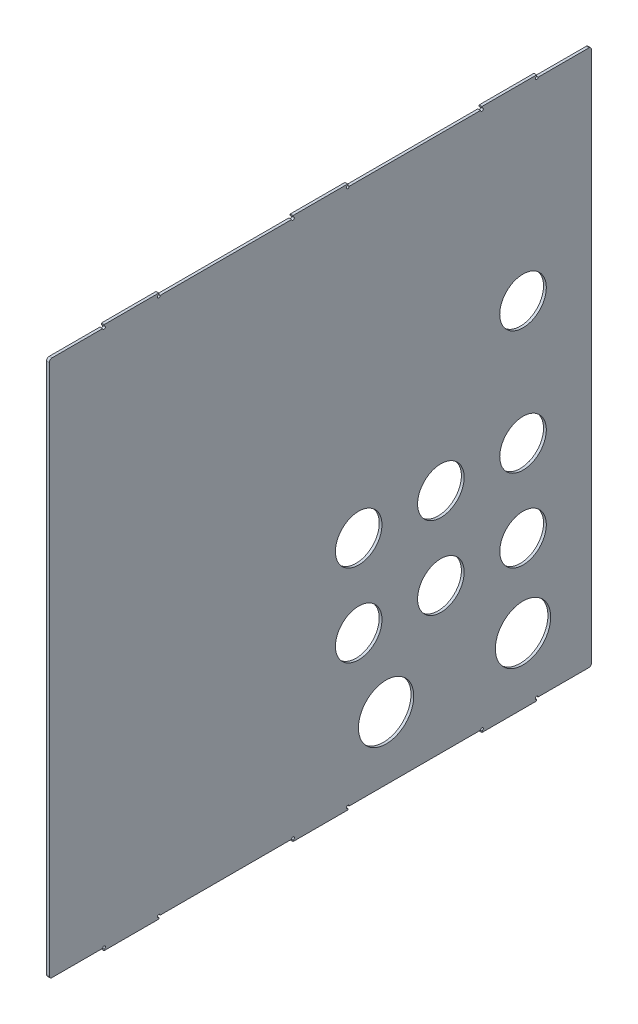
SolidWorks part; units mm, degrees
material "ASTM A36 Acier"
ref_plane "Front" through (0, 0, 0) normal (0, 0, 1) x (1, 0, 0)
ref_plane "Top" through (0, 0, 0) normal (0, 1, 0) x (1, 0, 0)
ref_plane "Right" through (0, 0, 0) normal (1, 0, 0) x (0, 0, -1)
sketch "Esquisse1" plane through (0, 0, 0) normal (1, 0, 0) x (0, 0, -1)
  line L0 (0, 99) -> (0, 0) construction
  line L1 (-99, -98) -> (-79, -98)
  line L2 (-99, -98) -> (-99, 98)
  line L3 (-99, 98) -> (-79, 98)
  line L4 (99, -98) -> (99, 98)
  line L5 (-99, -98) -> (99, 98) construction
  line L6 (-99, 98) -> (99, -98) construction
  line L8 (-10, 98) -> (-10, 99)
  line L9 (-10, 99) -> (10, 99)
  line L10 (10, 98) -> (10, 99)
  line L12 (59, 98) -> (59, 99)
  line L13 (59, 99) -> (79, 99)
  line L14 (79, 98) -> (79, 99)
  line L16 (-79, 98) -> (-79, 99)
  line L17 (-79, 99) -> (-59, 99)
  line L18 (-59, 98) -> (-59, 99)
  line L19 (-59, 98) -> (-10, 98)
  line L20 (10, 98) -> (59, 98)
  line L21 (79, 98) -> (99, 98)
  line L22 (-4.7942, 0) -> (-50004.7942, 0) construction
  line L23 (79, -98) -> (79, -99)
  line L24 (59, -99) -> (79, -99)
  line L25 (59, -98) -> (59, -99)
  line L26 (10, -98) -> (10, -99)
  line L27 (-10, -99) -> (10, -99)
  line L28 (-10, -98) -> (-10, -99)
  line L29 (-59, -98) -> (-59, -99)
  line L30 (-79, -98) -> (-79, -99)
  line L31 (-79, -99) -> (-59, -99)
  line L32 (-59, -98) -> (-10, -98)
  line L33 (10, -98) -> (59, -98)
  line L34 (79, -98) -> (99, -98)
  point P0 (0, 0)
  dimension "D1" = 196
  dimension "D2" = 198
  dimension "D3" = 1
  dimension "D4" = 20
  dimension "D5" = 20
  dimension "D6" = 20
base flange "Tôle de base pliée1" sketch "Esquisse1" thickness 1 reverse thickness direction no parameters "D1"=0.7366
sketch "Esquisse2" plane through (-1, 0, 0) normal (-1, 0, 0) x (0, 0, 1)
  line L12 (-99, 98) -> (-151.518, -98)
  line L13 (79, 98) -> (99, 98) construction
  line L14 (-99, -98) -> (-99, 98) construction
  line L15 (-151.518, -98) -> (-99, -98)
  line L16 (-99, -98) -> (-99, 98)
  line L17 (99, -98) -> (79, -98) construction
  dimension "D1" = 15
base flange "Patte1" [suppressed] sketch "Esquisse2" thickness 1 reverse thickness direction no parameters "D1"=0.7366
sketch "Esquisse4" plane through (-1, 0, 0) normal (-1, 0, 0) x (0, 0, 1)
  line L0 (72.0915, -45) -> (13.3317, -45) construction
  line L1 (67.0754, -15) -> (-49932.9246, -15) construction
  line L2 (-74, -75) -> (-74, -45) construction
  line L3 (-14, -15) -> (-14, -45) construction
  line L4 (99, 30) -> (-93.4567, 30) construction
  line L5 (-14, -45) -> (-14, 30) construction
  line L6 (-99, -98) -> (-99, 98) construction
  line L8 (-74, 30) -> (-74, -45) construction
  line L9 (-74, -75) -> (-24, -75) construction
  line L10 (-74, -45) -> (-44, -45) construction
  circle A0 centre (-14, -15) radius 8.5
  circle A1 centre (-14, -45) radius 8.5
  circle A2 centre (-44, -15) radius 8.5
  circle A3 centre (-44, -45) radius 8.5
  circle A4 centre (-74, -45) radius 8.5
  circle A8 centre (-74, 30) radius 8.5
  circle A9 centre (-74, -75) radius 10.1
  circle A11 centre (-74, -15) radius 8.5
  circle A12 centre (-24, -75) radius 10.1
  dimension "D3" = 17
  dimension "D4" = 30
  dimension "D7" = 30
  dimension "D10" = 17
  dimension "D11" = 15
  dimension "D13" = 30
  dimension "D14" = 20.2
  dimension "D2" = 45
  dimension "D5" = 0
  dimension "D6" = 0
  dimension "D8" = 30
  dimension "D9" = 50
  dimension "D12" = 25
  dimension "D15" = 75
extrude "Enlèv. mat.-Extru.1" cut sketch "Esquisse4" against normal through all normal cut yes
ref_plane "Plan1" through (-1, 0, 0) normal (-1, 0, 0) x (0, 0, 1)
sketch "Esquisse11" plane through (-1, 0, 0) normal (-1, 0, 0) x (0, 0, 1)
  line L0 (-109.0261, 5) -> (49890.9739, 5) construction
  line L1 (-114.3569, -5) -> (49885.6431, -5) construction
  line L2 (-74, 30) -> (-74, -5) construction
  line L3 (-89.6603, 42) -> (9.9385, 42) construction
  line L4 (-74, -15) -> (-74, -2) construction
  line L5 (-128.3704, 10) -> (49871.6296, 10) construction
  line L6 (-74.568, -2) -> (-11.5081, -2) construction
  line L7 (-44, -15) -> (-44, -2) construction
  line L8 (-14, -15) -> (-14, -2) construction
  line L9 (-167.5798, -33) -> (49832.4202, -33) construction
  line L10 (-74, -45) -> (-74, -33) construction
  line L11 (-44, -45) -> (-44, -33) construction
  line L12 (-14, -45) -> (-14, -33) construction
  line L13 (-99, -98) -> (-99, 98) construction
  circle A0 centre (-44, -15) radius 8.5 construction
  circle A1 centre (-74, -15) radius 8.5 construction
  circle A2 centre (-14, -45) radius 8.5 construction
  text T0 "THERMOCOUPLES" font "Varela Round" height in points 22
  text T4 "HEATERS" font "Varela Round" height in points 22
  text T5 "2" font "Varela Round" height in points 22
  text T6 "3" font "Varela Round" height in points 22
  text T7 "4" font "Varela Round" height in points 22
  text T8 "5" font "Varela Round" height in points 22
  text T9 "6" font "Varela Round" height in points 22
  text T10 "1" font "Varela Round" height in points 22
  dimension "D1" = 5
  dimension "D2" = 10
  dimension "D3" = 12
  dimension "D4" = 31
  dimension "D5" = 2.5
  dimension "D6" = 25
  dimension "D7" = 12
  dimension "D8" = 2.5
  dimension "D9" = 2.5
  dimension "D10" = 12
  dimension "D11" = 2.5
  dimension "D12" = 2.5
  dimension "D13" = 2.5
extrude "Enlèv. mat.-Extru.2" cut sketch "Esquisse11" against normal blind 0.5 normal cut yes
sketch "Esquisse12" plane through (0, 0, 0) normal (1, 0, 0) x (0, 0, -1)
  line L0 (0, 0) -> (-50000, 0) construction
  circle A0 centre (-79, 98) radius 0.5
  circle A1 centre (-59, 98) radius 0.5
  circle A2 centre (-10, 98) radius 0.5
  circle A3 centre (10, 98) radius 0.5
  circle A4 centre (59, 98) radius 0.5
  circle A5 centre (79, 98) radius 0.5
  circle A6 centre (79, -98) radius 0.5
  circle A7 centre (59, -98) radius 0.5
  circle A8 centre (10, -98) radius 0.5
  circle A9 centre (-10, -98) radius 0.5
  circle A10 centre (-59, -98) radius 0.5
  circle A11 centre (-79, -98) radius 0.5
  dimension "D1" = 1
extrude "Enlèv. mat.-Extru.3" cut sketch "Esquisse12" against normal through all normal cut yes
fillet "Congé1" radius 1 4 edges at (-0.5, -98, 99) (-0.5, -98, -99) (-0.5, 98, -99) (-0.5, 98, 99)
sketch "Lignes de pliage1" [suppressed] plane through (0, 0, 0) normal (0, 1, 0) x (1, 0, 0)
sketch "Cube de visualisation1" [suppressed] plane through (0, 0, 0) normal (0, 1, 0) x (1, 0, 0)
sheet metal parameters "Tôlerie1" thickness 1 parameters "D1"=0.7366
flat pattern "Etat déplié1" [suppressed]
sketch "Lignes de pliage2" plane through (0, 0, 0) normal (0, 1, 0) x (1, 0, 0)
sketch3d "Cube de visualisation2" [suppressed]
  line L0 (99, -99, 0) -> (-99, -99, 0) construction
  line L1 (99, 99, 0) -> (-99, 99, 0) construction
  line L2 (99, -99, 0) -> (99, 99, 0) construction
  line L3 (-99, -99, 0) -> (-99, 99, 0) construction
sheet metal parameters "Tôlerie2" thickness 1 parameters "D1"=0.7366
flat pattern "Etat déplié2"
sketch "Lignes de pliage3" plane through (0, 0, 0) normal (0, 1, 0) x (1, 0, 0)
sketch3d "Cube de visualisation3" [suppressed]
  line L0 (152.0539, -99, 0) -> (-99, -99, 0) construction
  line L1 (152.0539, 99, 0) -> (-99, 99, 0) construction
  line L2 (152.0539, -99, 0) -> (152.0539, 99, 0) construction
  line L3 (-99, -99, 0) -> (-99, 99, 0) construction
sheet metal parameters "Tôlerie3" thickness 1 parameters "D1"=0.7366, "D7"=2
flat pattern "Etat déplié1" [suppressed]
sketch "Lignes de pliage2" plane through (0, 0, 0) normal (0, 1, 0) x (1, 0, 0)
sketch3d "Cube de visualisation2" [suppressed]
  line L0 (99, -99, 0) -> (-99, -99, 0) construction
  line L1 (99, 99, 0) -> (-99, 99, 0) construction
  line L2 (99, -99, 0) -> (99, 99, 0) construction
  line L3 (-99, -99, 0) -> (-99, 99, 0) construction
sketch "Esquisse11-1" [suppressed] plane through (-2, 0, 0) normal (-1, 0, 0) x (0, 0, 1)
  line L0 (-109.0261, 15) -> (49890.9739, 15) construction
  line L1 (-114.3569, 5) -> (49885.6431, 5) construction
  line L2 (-74, -10) -> (-74, 5) construction
  line L3 (-49, -10) -> (-49, 5) construction
  line L4 (-24, -10) -> (-24, 5) construction
  line L5 (-128.3704, -30) -> (49871.6296, -30) construction
  circle A0 centre (-61.5, -55) radius 8.5 construction
  text T0 "THERMOCOUPLES" font "Century Gothic" height in points 24
  text T1 "1"
  text T2 "2"
  text T3 "3"
  text T4 "HEATERS"
  dimension "D1" = 15
  dimension "D2" = 10
  dimension "D3" = 2.5
  dimension "D4" = 2.5
  dimension "D5" = 2.5
  dimension "D6" = 25
sheet metal parameters "Tôlerie4" thickness 1 parameters "D1"=0.7366, "D7"=2
flat pattern "Etat déplié1" [suppressed]
sketch "Lignes de pliage2" plane through (0, 0, 0) normal (0, 1, 0) x (1, 0, 0)
sketch3d "Cube de visualisation2" [suppressed]
  line L0 (99, 100, 0) -> (99, -100, 0) construction
  line L1 (-99, 100, 0) -> (-99, -100, 0) construction
  line L2 (99, 100, 0) -> (-99, 100, 0) construction
  line L3 (99, -100, 0) -> (-99, -100, 0) construction
sketch "Esquisse11-1" [suppressed] plane through (-2, 0, 0) normal (-1, 0, 0) x (0, 0, 1)
  line L0 (-109.0261, 5) -> (49890.9739, 5) construction
  line L1 (-114.3569, -5) -> (49885.6431, -5) construction
  line L2 (-74, -10) -> (-74, -5) construction
  line L4 (-74, -55) -> (-74, -42) construction
  line L5 (-128.3704, -30) -> (49871.6296, -30) construction
  line L6 (-79.568, -42) -> (-16.5081, -42) construction
  line L7 (-49, -55) -> (-49, -42) construction
  line L8 (-24, -55) -> (-24, -42) construction
  line L9 (-167.5798, -73) -> (49832.4202, -73) construction
  line L10 (-74, -85) -> (-74, -73) construction
  line L11 (-49, -85) -> (-49, -73) construction
  line L12 (-24, -85) -> (-24, -73) construction
  circle A0 centre (-49, -55) radius 8.5 construction
  circle A2 centre (-24, -85) radius 8.5 construction
  text T0 "THERMOCOUPLES" font "Century Gothic" height in points 24
  text T4 "HEATERS"
  text T5 "2" font "Century Gothic" height in points 24
  text T6 "3" font "Century Gothic" height in points 24
  text T7 "4" font "Century Gothic" height in points 24
  text T8 "5" font "Century Gothic" height 6.35
  text T9 "6" font "Century Gothic" height in points 24
  text T10 "1" font "Century Gothic" height in points 24
  dimension "D1" = 5
  dimension "D2" = 10
  dimension "D5" = 2.5
  dimension "D6" = 25
  dimension "D7" = 12
  dimension "D8" = 2.5
  dimension "D9" = 2.5
  dimension "D10" = 12
  dimension "D11" = 2.5
  dimension "D12" = 2.5
  dimension "D13" = 2.5
sheet metal parameters "Tôlerie5" thickness 1 parameters "D1"=0.7366, "D7"=2
flat pattern "Etat déplié1" [suppressed]
sketch "Lignes de pliage2" plane through (0, 0, 0) normal (0, 1, 0) x (1, 0, 0)
sketch3d "Cube de visualisation2" [suppressed]
  line L0 (99, 99, 0) -> (99, -99, 0) construction
  line L1 (-99, 99, 0) -> (-99, -99, 0) construction
  line L2 (99, 99, 0) -> (-99, 99, 0) construction
  line L3 (99, -99, 0) -> (-99, -99, 0) construction
sketch "Esquisse11-1" [suppressed] plane through (-1, 0, 0) normal (-1, 0, 0) x (0, 0, 1)
  line L0 (-109.0261, 5) -> (49890.9739, 5) construction
  line L1 (-114.3569, -5) -> (49885.6431, -5) construction
  line L2 (-74, 30) -> (-74, -5) construction
  line L3 (-89.6603, 42) -> (9.9385, 42) construction
  line L4 (-74, -15) -> (-74, -2) construction
  line L5 (-128.3704, 10) -> (49871.6296, 10) construction
  line L6 (-74.568, -2) -> (-11.5081, -2) construction
  line L7 (-44, -15) -> (-44, -2) construction
  line L8 (-14, -15) -> (-14, -2) construction
  line L9 (-167.5798, -33) -> (49832.4202, -33) construction
  line L10 (-74, -45) -> (-74, -33) construction
  line L11 (-44, -45) -> (-44, -33) construction
  line L12 (-14, -45) -> (-14, -33) construction
  line L13 (-99, -97) -> (-99, 97) construction
  circle A0 centre (-44, -15) radius 8.5 construction
  circle A2 centre (-14, -45) radius 8.5 construction
  text T0 "THERMOCOUPLES" font "Varela Round" height in points 22
  text T4 "HEATERS" font "Varela Round" height in points 22
  text T5 "2" font "Varela Round" height in points 22
  text T6 "3" font "Varela Round" height in points 22
  text T7 "4" font "Varela Round" height in points 22
  text T8 "5" font "Varela Round" height in points 22
  text T9 "6" font "Varela Round" height in points 22
  text T10 "1" font "Varela Round" height in points 22
  dimension "D1" = 5
  dimension "D2" = 10
  dimension "D3" = 12
  dimension "D4" = 31
  dimension "D5" = 2.5
  dimension "D6" = 25
  dimension "D7" = 12
  dimension "D8" = 2.5
  dimension "D9" = 2.5
  dimension "D10" = 12
  dimension "D11" = 2.5
  dimension "D12" = 2.5
  dimension "D13" = 2.5
